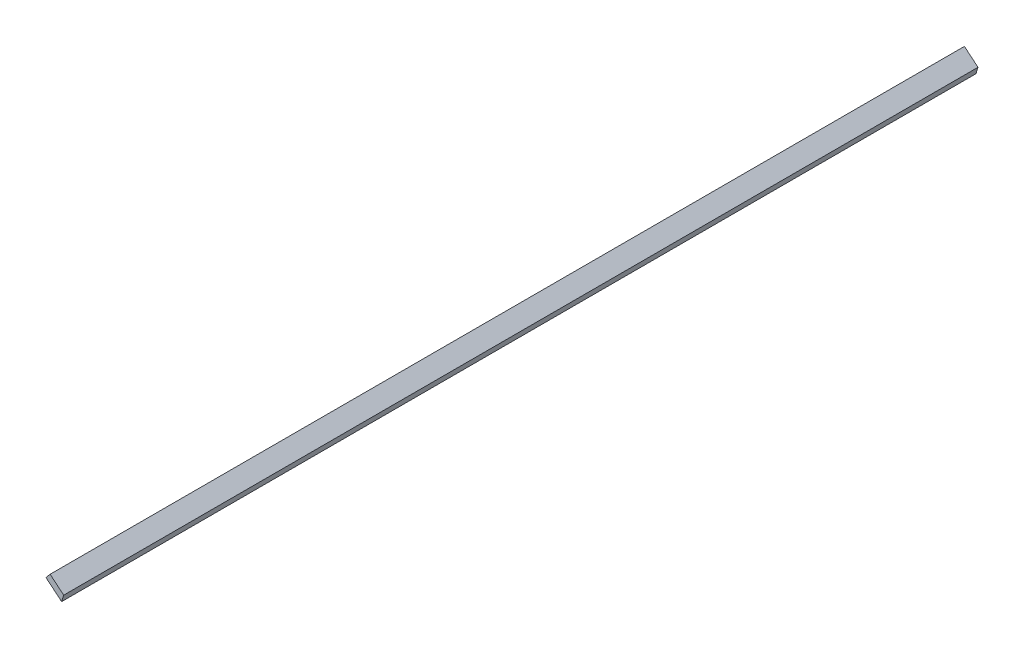
SolidWorks part; units mm, degrees
ref_plane "Front Plane" through (0, 0, 0) normal (0, 0, 1) x (1, 0, 0)
ref_plane "Top Plane" through (0, 0, 0) normal (0, 1, 0) x (1, 0, 0)
ref_plane "Right Plane" through (0, 0, 0) normal (1, 0, 0) x (0, 0, -1)
sketch "Sketch1" plane through (0, 0, 0) normal (0, 0, 1) x (1, 0, 0)
  line L0 (0, 0) -> (2.0444, 6.5621)
  line L1 (2.0444, 6.5621) -> (-11.3505, 17.7238)
  line L2 (-11.3505, 17.7238) -> (-15.4155, 12.8455)
  line L3 (-15.4155, 12.8455) -> (0, 0)
  dimension "D1" = 6.35
  dimension "D2" = 90
  dimension "D3" = 67.5
  dimension "D4" = 20.066
extrude "Boss-Extrude1" add sketch "Sketch1" along normal blind 901.7
